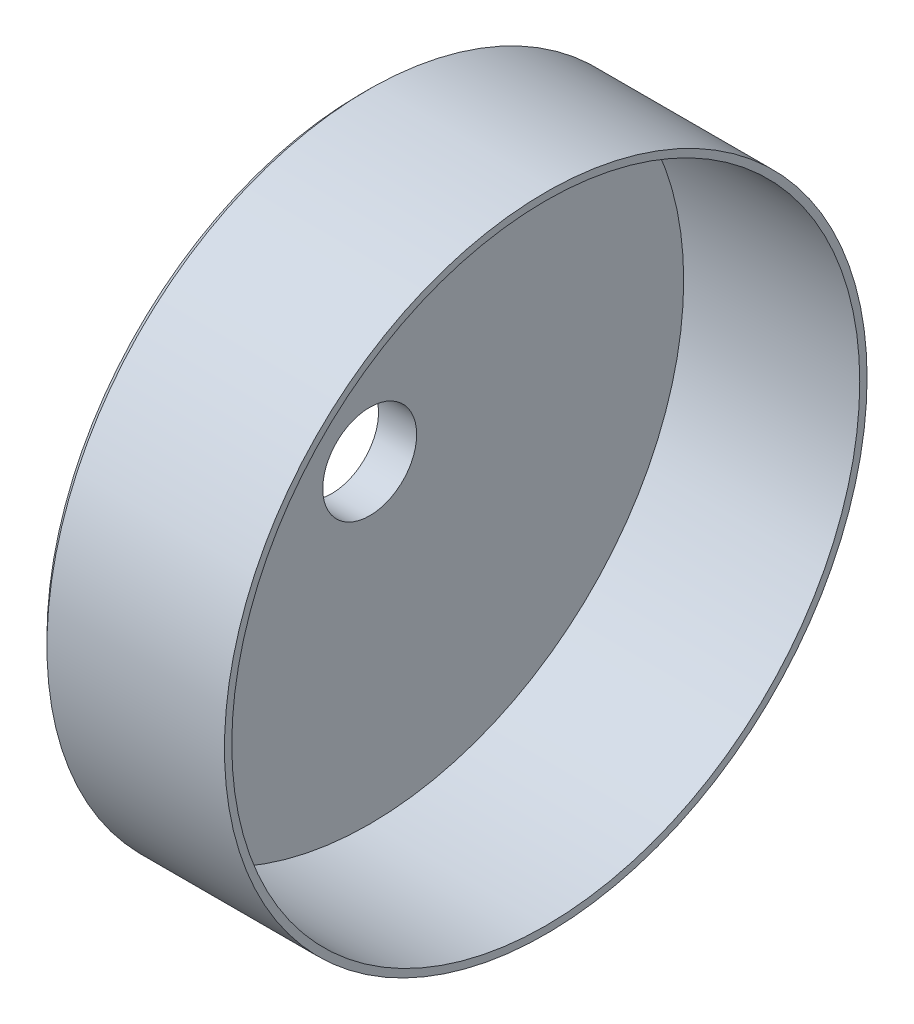
SolidWorks part; units mm, degrees
ref_plane "Front Plane" through (0, 0, 0) normal (1, 0, 0) x (0, 1, 0)
ref_plane "Top Plane" through (0, 0, 0) normal (0, 0, 1) x (0, 1, 0)
ref_plane "Right Plane" through (0, 0, 0) normal (0, 1, 0) x (-1, 0, 0)
sketch "Sketch1" plane through (0, 0, 0) normal (1, 0, 0) x (0, 1, 0)
  circle A0 centre (0, 0) radius 21.9
  dimension "D1" = 43.8
extrude "Boss-Extrude1" add sketch "Sketch1" along normal blind 0.6
sketch "Sketch2" plane through (0.6, 0, 0) normal (1, 0, 0) x (0, 1, 0)
  circle A0 centre (0, 0) radius 21.4
  circle A2 centre (0, 0) radius 21.9
  dimension "D1" = 42.8
extrude "Boss-Extrude2" add sketch "Sketch2" along normal blind 12
sketch "Sketch3" plane through (0, 0, 0) normal (-1, 0, 0) x (0, -1, 0)
  circle A0 centre (0, 0) radius 3.2
extrude "Cut-Extrude1" cut sketch "Sketch3" against normal blind 12
sketch "Sketch4" plane through (0, 0, 0) normal (-1, 0, 0) x (0, -1, 0)
  circle A0 centre (0, 0) radius 3.9
  circle A2 centre (0, 0) radius 3.2
  dimension "D1" = 7.8
extrude "Boss-Extrude3" add sketch "Sketch4" along normal blind 2
fillet "Fillet1" radius 2 1 edges at (0, 0, -3.9)
chamfer "Chamfer1" distance 0.5 angle 45 1 edges at (0, 0, -21.9)
